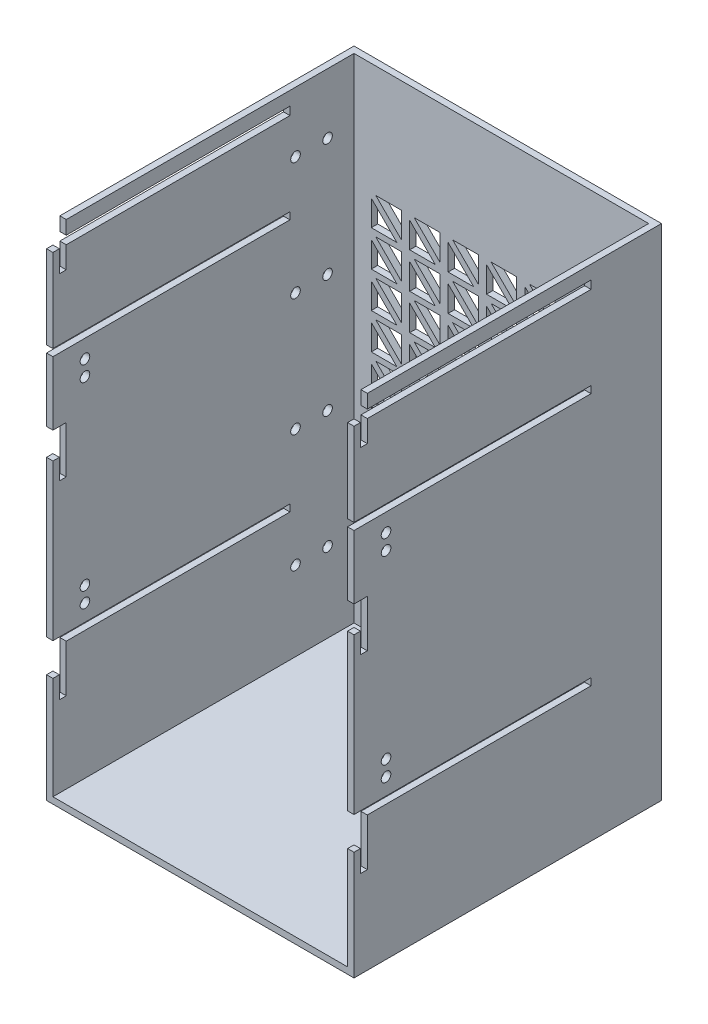
SolidWorks part; units mm, degrees
note: The reader was unsure of these and kept them because the rebuilt part matched: shared geometry of "Sketch7<2>".
ref_plane "Front Plane" through (0, 0, 0) normal (0, 0, 1) x (1, 0, 0)
ref_plane "Top Plane" through (0, 0, 0) normal (0, 1, 0) x (1, 0, 0)
ref_plane "Right Plane" through (0, 0, 0) normal (1, 0, 0) x (0, 0, -1)
sketch "Sketch1" plane through (0, 0, 0) normal (0, 1, 0) x (1, 0, 0)
  line L1 (0, 0) -> (152.4, 0)
  line L2 (0, 0) -> (0, 152.4)
  line L3 (0, 152.4) -> (152.4, 152.4)
  line L4 (152.4, 0) -> (152.4, 152.4)
  dimension "D1" = 152.4
  dimension "D2" = 152.4
extrude "Boss-Extrude1" add sketch "Sketch1" along normal blind 247.65
shell "Shell1" thickness 3.175
ref_plane "Plane1" through (0, 0, -117.475) normal (0, 0, 1) x (1, 0, 0)
sketch "Sketch3" plane through (0, 0, -117.475) normal (0, 0, 1) x (1, 0, 0)
  line L1 (0, 66.675) -> (152.4, 66.675)
  line L2 (0, 66.675) -> (0, 70.1548)
  line L3 (0, 70.1548) -> (152.4, 70.1548)
  line L4 (152.4, 66.675) -> (152.4, 70.1548)
  line L5 (0, 240.8936) -> (152.4, 240.8936)
  line L6 (3.175, 3.175) -> (149.225, 3.175) construction
  line L8 (0, 195.5546) -> (152.4, 195.5546)
  line L9 (0, 195.5546) -> (0, 192.0748)
  line L10 (0, 192.0748) -> (152.4, 192.0748)
  line L11 (152.4, 195.5546) -> (152.4, 192.0748)
  line L12 (152.4, 247.65) -> (152.4, 0) construction
  line L13 (0, 247.65) -> (0, 0) construction
  line L14 (0, 240.8936) -> (0, 236.8296)
  line L15 (0, 236.8296) -> (152.4, 236.8296)
  line L16 (152.4, 240.8936) -> (152.4, 236.8296)
  dimension "D1" = 3.4798
  dimension "D2" = 63.5
  dimension "D3" = 121.92
  dimension "D4" = 41.275
  dimension "D5" = 4.064
extrude "Cut-Extrude1" cut sketch "Sketch3" along normal up to next
sketch "Sketch4" plane through (152.4, 0, 0) normal (1, 0, 0) x (0, 0, -1)
  line L0 (0, 240.8936) -> (117.475, 240.8936) construction
  line L1 (0, 247.65) -> (6.604, 247.65)
  line L2 (0, 247.65) -> (0, 240.8936)
  line L3 (0, 240.8936) -> (6.604, 240.8936)
  line L4 (6.604, 247.65) -> (6.604, 240.8936)
  line L5 (0, 236.8296) -> (117.475, 236.8296) construction
  line L6 (3.175, 236.8296) -> (6.604, 236.8296)
  line L7 (3.175, 236.8296) -> (3.175, 226.06)
  line L8 (3.175, 226.06) -> (6.604, 226.06)
  line L9 (6.604, 236.8296) -> (6.604, 226.06)
  line L10 (0, 236.8296) -> (0, 195.5546) construction
  line L11 (6.604, 66.675) -> (6.604, 43.2054)
  line L12 (0, 66.675) -> (6.604, 66.675)
  line L13 (0, 66.675) -> (0, 53.975)
  line L14 (0, 53.975) -> (3.175, 53.975)
  line L18 (6.604, 43.2054) -> (3.175, 43.2054)
  line L19 (3.175, 53.975) -> (3.175, 43.2054)
  line L20 (0, 247.65) -> (152.4, 247.65) construction
  line L21 (0, 192.0748) -> (0, 70.1548) construction
  line L23 (3.175, 147.32) -> (3.175, 137.16)
  line L24 (3.175, 137.16) -> (6.604, 137.16)
  line L25 (6.604, 160.528) -> (6.604, 137.16)
  line L28 (3.175, 147.32) -> (0, 147.32)
  line L29 (0, 160.528) -> (0, 147.32)
  line L30 (0, 160.528) -> (6.604, 160.528)
  point P29 (3.175, 231.4448)
  dimension "D1" = 3.175
  dimension "D2" = 3.429
  dimension "D3" = 21.59
  dimension "D4" = 88.9
  dimension "D5" = 12.7
  dimension "D6" = 23.368
  dimension "D7" = 13.208
extrude "Cut-Extrude2" cut sketch "Sketch4" against normal through all
sketch "Sketch5" plane through (0, 0, -152.4) normal (0, 0, -1) x (-1, 0, 0)
  line L0 (-152.4, 0) -> (0, 0) construction
  line L1 (-152.4, 247.65) -> (-152.4, 0) construction
  circle A0 centre (-115.8748, 30.1752) radius 4.8895
  dimension "D1" = 9.779
  dimension "D2" = 30.1752
  dimension "D3" = 36.5252
extrude "Cut-Extrude3" cut sketch "Sketch5" against normal up to next
sketch "Sketch6" plane through (0, 0, -149.225) normal (0, 0, 1) x (1, 0, 0)
  line L0 (140.97, 192.0748) -> (140.97, 179.3748)
  line L1 (140.97, 179.3748) -> (128.27, 192.0748)
  line L2 (128.27, 192.0748) -> (140.97, 192.0748)
  line L3 (149.225, 192.0748) -> (149.225, 160.528) construction
  line L4 (126.0249, 192.0748) -> (140.97, 177.1297) construction
  line L5 (138.7249, 177.1297) -> (126.0249, 189.8297)
  line L6 (126.0249, 177.1297) -> (138.7249, 177.1297)
  line L7 (126.0249, 189.8297) -> (126.0249, 177.1297)
  line L8 (149.225, 192.0748) -> (152.4, 192.0748) construction
  line L9 (140.97, 174.2948) -> (140.97, 161.5948)
  line L10 (140.97, 161.5948) -> (128.27, 174.2948)
  line L11 (128.27, 174.2948) -> (140.97, 174.2948)
  line L12 (138.7249, 159.3497) -> (126.0249, 172.0497)
  line L13 (126.0249, 172.0497) -> (126.0249, 159.3497)
  line L14 (126.0249, 159.3497) -> (138.7249, 159.3497)
  line L15 (140.97, 156.5148) -> (140.97, 143.8148)
  line L16 (140.97, 143.8148) -> (128.27, 156.5148)
  line L17 (128.27, 156.5148) -> (140.97, 156.5148)
  line L18 (138.7249, 141.5697) -> (126.0249, 154.2697)
  line L19 (126.0249, 154.2697) -> (126.0249, 141.5697)
  line L20 (126.0249, 141.5697) -> (138.7249, 141.5697)
  line L21 (140.97, 138.7348) -> (140.97, 126.0348)
  line L22 (140.97, 126.0348) -> (128.27, 138.7348)
  line L23 (128.27, 138.7348) -> (140.97, 138.7348)
  line L24 (138.7249, 123.7897) -> (126.0249, 136.4897)
  line L25 (126.0249, 136.4897) -> (126.0249, 123.7897)
  line L26 (126.0249, 123.7897) -> (138.7249, 123.7897)
  line L27 (140.97, 120.9548) -> (140.97, 108.2548)
  line L28 (140.97, 108.2548) -> (128.27, 120.9548)
  line L29 (128.27, 120.9548) -> (140.97, 120.9548)
  line L30 (138.7249, 106.0097) -> (126.0249, 118.7097)
  line L31 (126.0249, 118.7097) -> (126.0249, 106.0097)
  line L32 (126.0249, 106.0097) -> (138.7249, 106.0097)
  line L33 (140.97, 103.1748) -> (140.97, 90.4748)
  line L34 (140.97, 90.4748) -> (128.27, 103.1748)
  line L35 (128.27, 103.1748) -> (140.97, 103.1748)
  line L36 (138.7249, 88.2297) -> (126.0249, 100.9297)
  line L37 (126.0249, 100.9297) -> (126.0249, 88.2297)
  line L38 (126.0249, 88.2297) -> (138.7249, 88.2297)
  line L39 (140.97, 85.3948) -> (140.97, 72.6948)
  line L40 (140.97, 72.6948) -> (128.27, 85.3948)
  line L41 (128.27, 85.3948) -> (140.97, 85.3948)
  line L42 (138.7249, 70.4497) -> (126.0249, 83.1497)
  line L43 (126.0249, 83.1497) -> (126.0249, 70.4497)
  line L44 (126.0249, 70.4497) -> (138.7249, 70.4497)
  line L45 (121.92, 192.0748) -> (121.92, 179.3748)
  line L46 (121.92, 179.3748) -> (109.22, 192.0748)
  line L47 (109.22, 192.0748) -> (121.92, 192.0748)
  line L48 (119.6749, 177.1297) -> (106.9749, 189.8297)
  line L49 (106.9749, 177.1297) -> (119.6749, 177.1297)
  line L50 (106.9749, 189.8297) -> (106.9749, 177.1297)
  line L51 (121.92, 174.2948) -> (121.92, 161.5948)
  line L52 (121.92, 161.5948) -> (109.22, 174.2948)
  line L53 (109.22, 174.2948) -> (121.92, 174.2948)
  line L54 (119.6749, 159.3497) -> (106.9749, 172.0497)
  line L55 (106.9749, 172.0497) -> (106.9749, 159.3497)
  line L56 (106.9749, 159.3497) -> (119.6749, 159.3497)
  line L57 (121.92, 156.5148) -> (121.92, 143.8148)
  line L58 (121.92, 143.8148) -> (109.22, 156.5148)
  line L59 (109.22, 156.5148) -> (121.92, 156.5148)
  line L60 (119.6749, 141.5697) -> (106.9749, 154.2697)
  line L61 (106.9749, 154.2697) -> (106.9749, 141.5697)
  line L62 (106.9749, 141.5697) -> (119.6749, 141.5697)
  line L63 (121.92, 138.7348) -> (121.92, 126.0348)
  line L64 (121.92, 126.0348) -> (109.22, 138.7348)
  line L65 (109.22, 138.7348) -> (121.92, 138.7348)
  line L66 (119.6749, 123.7897) -> (106.9749, 136.4897)
  line L67 (106.9749, 136.4897) -> (106.9749, 123.7897)
  line L68 (106.9749, 123.7897) -> (119.6749, 123.7897)
  line L69 (121.92, 120.9548) -> (121.92, 108.2548)
  line L70 (121.92, 108.2548) -> (109.22, 120.9548)
  line L71 (109.22, 120.9548) -> (121.92, 120.9548)
  line L72 (119.6749, 106.0097) -> (106.9749, 118.7097)
  line L73 (106.9749, 118.7097) -> (106.9749, 106.0097)
  line L74 (106.9749, 106.0097) -> (119.6749, 106.0097)
  line L75 (121.92, 103.1748) -> (121.92, 90.4748)
  line L76 (121.92, 90.4748) -> (109.22, 103.1748)
  line L77 (109.22, 103.1748) -> (121.92, 103.1748)
  line L78 (119.6749, 88.2297) -> (106.9749, 100.9297)
  line L79 (106.9749, 100.9297) -> (106.9749, 88.2297)
  line L80 (106.9749, 88.2297) -> (119.6749, 88.2297)
  line L81 (121.92, 85.3948) -> (121.92, 72.6948)
  line L82 (121.92, 72.6948) -> (109.22, 85.3948)
  line L83 (109.22, 85.3948) -> (121.92, 85.3948)
  line L84 (119.6749, 70.4497) -> (106.9749, 83.1497)
  line L85 (106.9749, 83.1497) -> (106.9749, 70.4497)
  line L86 (106.9749, 70.4497) -> (119.6749, 70.4497)
  line L87 (102.87, 192.0748) -> (102.87, 179.3748)
  line L88 (102.87, 179.3748) -> (90.17, 192.0748)
  line L89 (90.17, 192.0748) -> (102.87, 192.0748)
  line L90 (100.6249, 177.1297) -> (87.9249, 189.8297)
  line L91 (87.9249, 177.1297) -> (100.6249, 177.1297)
  line L92 (87.9249, 189.8297) -> (87.9249, 177.1297)
  line L93 (102.87, 174.2948) -> (102.87, 161.5948)
  line L94 (102.87, 161.5948) -> (90.17, 174.2948)
  line L95 (90.17, 174.2948) -> (102.87, 174.2948)
  line L96 (100.6249, 159.3497) -> (87.9249, 172.0497)
  line L97 (87.9249, 172.0497) -> (87.9249, 159.3497)
  line L98 (87.9249, 159.3497) -> (100.6249, 159.3497)
  line L99 (102.87, 156.5148) -> (102.87, 143.8148)
  line L100 (102.87, 143.8148) -> (90.17, 156.5148)
  line L101 (90.17, 156.5148) -> (102.87, 156.5148)
  line L102 (100.6249, 141.5697) -> (87.9249, 154.2697)
  line L103 (87.9249, 154.2697) -> (87.9249, 141.5697)
  line L104 (87.9249, 141.5697) -> (100.6249, 141.5697)
  line L105 (102.87, 138.7348) -> (102.87, 126.0348)
  line L106 (102.87, 126.0348) -> (90.17, 138.7348)
  line L107 (90.17, 138.7348) -> (102.87, 138.7348)
  line L108 (100.6249, 123.7897) -> (87.9249, 136.4897)
  line L109 (87.9249, 136.4897) -> (87.9249, 123.7897)
  line L110 (87.9249, 123.7897) -> (100.6249, 123.7897)
  line L111 (102.87, 120.9548) -> (102.87, 108.2548)
  line L112 (102.87, 108.2548) -> (90.17, 120.9548)
  line L113 (90.17, 120.9548) -> (102.87, 120.9548)
  line L114 (100.6249, 106.0097) -> (87.9249, 118.7097)
  line L115 (87.9249, 118.7097) -> (87.9249, 106.0097)
  line L116 (87.9249, 106.0097) -> (100.6249, 106.0097)
  line L117 (102.87, 103.1748) -> (102.87, 90.4748)
  line L118 (102.87, 90.4748) -> (90.17, 103.1748)
  line L119 (90.17, 103.1748) -> (102.87, 103.1748)
  line L120 (100.6249, 88.2297) -> (87.9249, 100.9297)
  line L121 (87.9249, 100.9297) -> (87.9249, 88.2297)
  line L122 (87.9249, 88.2297) -> (100.6249, 88.2297)
  line L123 (102.87, 85.3948) -> (102.87, 72.6948)
  line L124 (102.87, 72.6948) -> (90.17, 85.3948)
  line L125 (90.17, 85.3948) -> (102.87, 85.3948)
  line L126 (100.6249, 70.4497) -> (87.9249, 83.1497)
  line L127 (87.9249, 83.1497) -> (87.9249, 70.4497)
  line L128 (87.9249, 70.4497) -> (100.6249, 70.4497)
  line L129 (83.82, 192.0748) -> (83.82, 179.3748)
  line L130 (83.82, 179.3748) -> (71.12, 192.0748)
  line L131 (71.12, 192.0748) -> (83.82, 192.0748)
  line L132 (81.5749, 177.1297) -> (68.8749, 189.8297)
  line L133 (68.8749, 177.1297) -> (81.5749, 177.1297)
  line L134 (68.8749, 189.8297) -> (68.8749, 177.1297)
  line L135 (83.82, 174.2948) -> (83.82, 161.5948)
  line L136 (83.82, 161.5948) -> (71.12, 174.2948)
  line L137 (71.12, 174.2948) -> (83.82, 174.2948)
  line L138 (81.5749, 159.3497) -> (68.8749, 172.0497)
  line L139 (68.8749, 172.0497) -> (68.8749, 159.3497)
  line L140 (68.8749, 159.3497) -> (81.5749, 159.3497)
  line L141 (83.82, 156.5148) -> (83.82, 143.8148)
  line L142 (83.82, 143.8148) -> (71.12, 156.5148)
  line L143 (71.12, 156.5148) -> (83.82, 156.5148)
  line L144 (81.5749, 141.5697) -> (68.8749, 154.2697)
  line L145 (68.8749, 154.2697) -> (68.8749, 141.5697)
  line L146 (68.8749, 141.5697) -> (81.5749, 141.5697)
  line L147 (83.82, 138.7348) -> (83.82, 126.0348)
  line L148 (83.82, 126.0348) -> (71.12, 138.7348)
  line L149 (71.12, 138.7348) -> (83.82, 138.7348)
  line L150 (81.5749, 123.7897) -> (68.8749, 136.4897)
  line L151 (68.8749, 136.4897) -> (68.8749, 123.7897)
  line L152 (68.8749, 123.7897) -> (81.5749, 123.7897)
  line L153 (83.82, 120.9548) -> (83.82, 108.2548)
  line L154 (83.82, 108.2548) -> (71.12, 120.9548)
  line L155 (71.12, 120.9548) -> (83.82, 120.9548)
  line L156 (81.5749, 106.0097) -> (68.8749, 118.7097)
  line L157 (68.8749, 118.7097) -> (68.8749, 106.0097)
  line L158 (68.8749, 106.0097) -> (81.5749, 106.0097)
  line L159 (83.82, 103.1748) -> (83.82, 90.4748)
  line L160 (83.82, 90.4748) -> (71.12, 103.1748)
  line L161 (71.12, 103.1748) -> (83.82, 103.1748)
  line L162 (81.5749, 88.2297) -> (68.8749, 100.9297)
  line L163 (68.8749, 100.9297) -> (68.8749, 88.2297)
  line L164 (68.8749, 88.2297) -> (81.5749, 88.2297)
  line L165 (83.82, 85.3948) -> (83.82, 72.6948)
  line L166 (83.82, 72.6948) -> (71.12, 85.3948)
  line L167 (71.12, 85.3948) -> (83.82, 85.3948)
  line L168 (81.5749, 70.4497) -> (68.8749, 83.1497)
  line L169 (68.8749, 83.1497) -> (68.8749, 70.4497)
  line L170 (68.8749, 70.4497) -> (81.5749, 70.4497)
  line L171 (64.77, 192.0748) -> (64.77, 179.3748)
  line L172 (64.77, 179.3748) -> (52.07, 192.0748)
  line L173 (52.07, 192.0748) -> (64.77, 192.0748)
  line L174 (62.5249, 177.1297) -> (49.8249, 189.8297)
  line L175 (49.8249, 177.1297) -> (62.5249, 177.1297)
  line L176 (49.8249, 189.8297) -> (49.8249, 177.1297)
  line L177 (64.77, 174.2948) -> (64.77, 161.5948)
  line L178 (64.77, 161.5948) -> (52.07, 174.2948)
  line L179 (52.07, 174.2948) -> (64.77, 174.2948)
  line L180 (62.5249, 159.3497) -> (49.8249, 172.0497)
  line L181 (49.8249, 172.0497) -> (49.8249, 159.3497)
  line L182 (49.8249, 159.3497) -> (62.5249, 159.3497)
  line L183 (64.77, 156.5148) -> (64.77, 143.8148)
  line L184 (64.77, 143.8148) -> (52.07, 156.5148)
  line L185 (52.07, 156.5148) -> (64.77, 156.5148)
  line L186 (62.5249, 141.5697) -> (49.8249, 154.2697)
  line L187 (49.8249, 154.2697) -> (49.8249, 141.5697)
  line L188 (49.8249, 141.5697) -> (62.5249, 141.5697)
  line L189 (64.77, 138.7348) -> (64.77, 126.0348)
  line L190 (64.77, 126.0348) -> (52.07, 138.7348)
  line L191 (52.07, 138.7348) -> (64.77, 138.7348)
  line L192 (62.5249, 123.7897) -> (49.8249, 136.4897)
  line L193 (49.8249, 136.4897) -> (49.8249, 123.7897)
  line L194 (49.8249, 123.7897) -> (62.5249, 123.7897)
  line L195 (64.77, 120.9548) -> (64.77, 108.2548)
  line L196 (64.77, 108.2548) -> (52.07, 120.9548)
  line L197 (52.07, 120.9548) -> (64.77, 120.9548)
  line L198 (62.5249, 106.0097) -> (49.8249, 118.7097)
  line L199 (49.8249, 118.7097) -> (49.8249, 106.0097)
  line L200 (49.8249, 106.0097) -> (62.5249, 106.0097)
  line L201 (64.77, 103.1748) -> (64.77, 90.4748)
  line L202 (64.77, 90.4748) -> (52.07, 103.1748)
  line L203 (52.07, 103.1748) -> (64.77, 103.1748)
  line L204 (62.5249, 88.2297) -> (49.8249, 100.9297)
  line L205 (49.8249, 100.9297) -> (49.8249, 88.2297)
  line L206 (49.8249, 88.2297) -> (62.5249, 88.2297)
  line L207 (64.77, 85.3948) -> (64.77, 72.6948)
  line L208 (64.77, 72.6948) -> (52.07, 85.3948)
  line L209 (52.07, 85.3948) -> (64.77, 85.3948)
  line L210 (62.5249, 70.4497) -> (49.8249, 83.1497)
  line L211 (49.8249, 83.1497) -> (49.8249, 70.4497)
  line L212 (49.8249, 70.4497) -> (62.5249, 70.4497)
  line L213 (45.72, 192.0748) -> (45.72, 179.3748)
  line L214 (45.72, 179.3748) -> (33.02, 192.0748)
  line L215 (33.02, 192.0748) -> (45.72, 192.0748)
  line L216 (43.4749, 177.1297) -> (30.7749, 189.8297)
  line L217 (30.7749, 177.1297) -> (43.4749, 177.1297)
  line L218 (30.7749, 189.8297) -> (30.7749, 177.1297)
  line L219 (45.72, 174.2948) -> (45.72, 161.5948)
  line L220 (45.72, 161.5948) -> (33.02, 174.2948)
  line L221 (33.02, 174.2948) -> (45.72, 174.2948)
  line L222 (43.4749, 159.3497) -> (30.7749, 172.0497)
  line L223 (30.7749, 172.0497) -> (30.7749, 159.3497)
  line L224 (30.7749, 159.3497) -> (43.4749, 159.3497)
  line L225 (45.72, 156.5148) -> (45.72, 143.8148)
  line L226 (45.72, 143.8148) -> (33.02, 156.5148)
  line L227 (33.02, 156.5148) -> (45.72, 156.5148)
  line L228 (43.4749, 141.5697) -> (30.7749, 154.2697)
  line L229 (30.7749, 154.2697) -> (30.7749, 141.5697)
  line L230 (30.7749, 141.5697) -> (43.4749, 141.5697)
  line L231 (45.72, 138.7348) -> (45.72, 126.0348)
  line L232 (45.72, 126.0348) -> (33.02, 138.7348)
  line L233 (33.02, 138.7348) -> (45.72, 138.7348)
  line L234 (43.4749, 123.7897) -> (30.7749, 136.4897)
  line L235 (30.7749, 136.4897) -> (30.7749, 123.7897)
  line L236 (30.7749, 123.7897) -> (43.4749, 123.7897)
  line L237 (45.72, 120.9548) -> (45.72, 108.2548)
  line L238 (45.72, 108.2548) -> (33.02, 120.9548)
  line L239 (33.02, 120.9548) -> (45.72, 120.9548)
  line L240 (43.4749, 106.0097) -> (30.7749, 118.7097)
  line L241 (30.7749, 118.7097) -> (30.7749, 106.0097)
  line L242 (30.7749, 106.0097) -> (43.4749, 106.0097)
  line L243 (45.72, 103.1748) -> (45.72, 90.4748)
  line L244 (45.72, 90.4748) -> (33.02, 103.1748)
  line L245 (33.02, 103.1748) -> (45.72, 103.1748)
  line L246 (43.4749, 88.2297) -> (30.7749, 100.9297)
  line L247 (30.7749, 100.9297) -> (30.7749, 88.2297)
  line L248 (30.7749, 88.2297) -> (43.4749, 88.2297)
  line L249 (45.72, 85.3948) -> (45.72, 72.6948)
  line L250 (45.72, 72.6948) -> (33.02, 85.3948)
  line L251 (33.02, 85.3948) -> (45.72, 85.3948)
  line L252 (43.4749, 70.4497) -> (30.7749, 83.1497)
  line L253 (30.7749, 83.1497) -> (30.7749, 70.4497)
  line L254 (30.7749, 70.4497) -> (43.4749, 70.4497)
  line L255 (26.67, 192.0748) -> (26.67, 179.3748)
  line L256 (26.67, 179.3748) -> (13.97, 192.0748)
  line L257 (13.97, 192.0748) -> (26.67, 192.0748)
  line L258 (24.4249, 177.1297) -> (11.7249, 189.8297)
  line L259 (11.7249, 177.1297) -> (24.4249, 177.1297)
  line L260 (11.7249, 189.8297) -> (11.7249, 177.1297)
  line L261 (26.67, 174.2948) -> (26.67, 161.5948)
  line L262 (26.67, 161.5948) -> (13.97, 174.2948)
  line L263 (13.97, 174.2948) -> (26.67, 174.2948)
  line L264 (24.4249, 159.3497) -> (11.7249, 172.0497)
  line L265 (11.7249, 172.0497) -> (11.7249, 159.3497)
  line L266 (11.7249, 159.3497) -> (24.4249, 159.3497)
  line L267 (26.67, 156.5148) -> (26.67, 143.8148)
  line L268 (26.67, 143.8148) -> (13.97, 156.5148)
  line L269 (13.97, 156.5148) -> (26.67, 156.5148)
  line L270 (24.4249, 141.5697) -> (11.7249, 154.2697)
  line L271 (11.7249, 154.2697) -> (11.7249, 141.5697)
  line L272 (11.7249, 141.5697) -> (24.4249, 141.5697)
  line L273 (26.67, 138.7348) -> (26.67, 126.0348)
  line L274 (26.67, 126.0348) -> (13.97, 138.7348)
  line L275 (13.97, 138.7348) -> (26.67, 138.7348)
  line L276 (24.4249, 123.7897) -> (11.7249, 136.4897)
  line L277 (11.7249, 136.4897) -> (11.7249, 123.7897)
  line L278 (11.7249, 123.7897) -> (24.4249, 123.7897)
  line L279 (26.67, 120.9548) -> (26.67, 108.2548)
  line L280 (26.67, 108.2548) -> (13.97, 120.9548)
  line L281 (13.97, 120.9548) -> (26.67, 120.9548)
  line L282 (24.4249, 106.0097) -> (11.7249, 118.7097)
  line L283 (11.7249, 118.7097) -> (11.7249, 106.0097)
  line L284 (11.7249, 106.0097) -> (24.4249, 106.0097)
  line L285 (26.67, 103.1748) -> (26.67, 90.4748)
  line L286 (26.67, 90.4748) -> (13.97, 103.1748)
  line L287 (13.97, 103.1748) -> (26.67, 103.1748)
  line L288 (24.4249, 88.2297) -> (11.7249, 100.9297)
  line L289 (11.7249, 100.9297) -> (11.7249, 88.2297)
  line L290 (11.7249, 88.2297) -> (24.4249, 88.2297)
  line L291 (26.67, 85.3948) -> (26.67, 72.6948)
  line L292 (26.67, 72.6948) -> (13.97, 85.3948)
  line L293 (13.97, 85.3948) -> (26.67, 85.3948)
  line L294 (24.4249, 70.4497) -> (11.7249, 83.1497)
  line L295 (11.7249, 83.1497) -> (11.7249, 70.4497)
  line L296 (11.7249, 70.4497) -> (24.4249, 70.4497)
  line L297 (149.225, 60.325) -> (3.175, 60.325) construction
  line L298 (149.225, 247.65) -> (149.225, 3.175) construction
  line L299 (3.175, 43.2054) -> (3.175, 66.675) construction
  line L300 (149.225, 3.175) -> (3.175, 3.175) construction
  line L301 (140.97, 60.325) -> (140.97, 47.625)
  line L302 (140.97, 47.625) -> (128.27, 60.325)
  line L303 (128.27, 60.325) -> (140.97, 60.325)
  line L304 (126.0249, 60.325) -> (147.432, 38.918) construction
  line L305 (126.0249, 58.0799) -> (126.0249, 45.3799)
  line L306 (138.7249, 45.3799) -> (126.0249, 58.0799)
  line L307 (126.0249, 45.3799) -> (138.7249, 45.3799)
  line L308 (121.92, 60.325) -> (121.92, 47.625)
  line L309 (121.92, 47.625) -> (109.22, 60.325)
  line L310 (109.22, 60.325) -> (121.92, 60.325)
  line L311 (106.9749, 58.0799) -> (106.9749, 45.3799)
  line L312 (119.6749, 45.3799) -> (106.9749, 58.0799)
  line L313 (106.9749, 45.3799) -> (119.6749, 45.3799)
  line L314 (102.87, 60.325) -> (102.87, 47.625)
  line L315 (102.87, 47.625) -> (90.17, 60.325)
  line L316 (90.17, 60.325) -> (102.87, 60.325)
  line L317 (87.9249, 58.0799) -> (87.9249, 45.3799)
  line L318 (100.6249, 45.3799) -> (87.9249, 58.0799)
  line L319 (87.9249, 45.3799) -> (100.6249, 45.3799)
  line L320 (83.82, 60.325) -> (83.82, 47.625)
  line L321 (83.82, 47.625) -> (71.12, 60.325)
  line L322 (71.12, 60.325) -> (83.82, 60.325)
  line L323 (68.8749, 58.0799) -> (68.8749, 45.3799)
  line L324 (81.5749, 45.3799) -> (68.8749, 58.0799)
  line L325 (68.8749, 45.3799) -> (81.5749, 45.3799)
  line L326 (64.77, 60.325) -> (64.77, 47.625)
  line L327 (64.77, 47.625) -> (52.07, 60.325)
  line L328 (52.07, 60.325) -> (64.77, 60.325)
  line L329 (49.8249, 58.0799) -> (49.8249, 45.3799)
  line L330 (62.5249, 45.3799) -> (49.8249, 58.0799)
  line L331 (49.8249, 45.3799) -> (62.5249, 45.3799)
  line L332 (45.72, 60.325) -> (45.72, 47.625)
  line L333 (45.72, 47.625) -> (33.02, 60.325)
  line L334 (33.02, 60.325) -> (45.72, 60.325)
  line L335 (30.7749, 58.0799) -> (30.7749, 45.3799)
  line L336 (43.4749, 45.3799) -> (30.7749, 58.0799)
  line L337 (30.7749, 45.3799) -> (43.4749, 45.3799)
  line L338 (26.67, 60.325) -> (26.67, 47.625)
  line L339 (26.67, 47.625) -> (13.97, 60.325)
  line L340 (13.97, 60.325) -> (26.67, 60.325)
  line L341 (11.7249, 58.0799) -> (11.7249, 45.3799)
  line L342 (24.4249, 45.3799) -> (11.7249, 58.0799)
  line L343 (11.7249, 45.3799) -> (24.4249, 45.3799)
  line L344 (102.87, 41.275) -> (102.87, 28.575)
  line L345 (102.87, 28.575) -> (90.17, 41.275)
  line L346 (90.17, 41.275) -> (102.87, 41.275)
  line L347 (87.9249, 39.0299) -> (87.9249, 26.3299)
  line L348 (100.6249, 26.3299) -> (87.9249, 39.0299)
  line L349 (87.9249, 26.3299) -> (100.6249, 26.3299)
  line L350 (83.82, 41.275) -> (83.82, 28.575)
  line L351 (83.82, 28.575) -> (71.12, 41.275)
  line L352 (71.12, 41.275) -> (83.82, 41.275)
  line L353 (68.8749, 39.0299) -> (68.8749, 26.3299)
  line L354 (81.5749, 26.3299) -> (68.8749, 39.0299)
  line L355 (68.8749, 26.3299) -> (81.5749, 26.3299)
  line L356 (64.77, 41.275) -> (64.77, 28.575)
  line L357 (64.77, 28.575) -> (52.07, 41.275)
  line L358 (52.07, 41.275) -> (64.77, 41.275)
  line L359 (49.8249, 39.0299) -> (49.8249, 26.3299)
  line L360 (62.5249, 26.3299) -> (49.8249, 39.0299)
  line L361 (49.8249, 26.3299) -> (62.5249, 26.3299)
  line L362 (45.72, 41.275) -> (45.72, 28.575)
  line L363 (45.72, 28.575) -> (33.02, 41.275)
  line L364 (33.02, 41.275) -> (45.72, 41.275)
  line L365 (30.7749, 39.0299) -> (30.7749, 26.3299)
  line L366 (43.4749, 26.3299) -> (30.7749, 39.0299)
  line L367 (30.7749, 26.3299) -> (43.4749, 26.3299)
  line L368 (26.67, 41.275) -> (26.67, 28.575)
  line L369 (26.67, 28.575) -> (13.97, 41.275)
  line L370 (13.97, 41.275) -> (26.67, 41.275)
  line L371 (11.7249, 39.0299) -> (11.7249, 26.3299)
  line L372 (24.4249, 26.3299) -> (11.7249, 39.0299)
  line L373 (11.7249, 26.3299) -> (24.4249, 26.3299)
  line L374 (126.0249, 26.3299) -> (138.7249, 26.3299)
  line L375 (126.0249, 39.0299) -> (126.0249, 26.3299)
  line L376 (138.7249, 26.3299) -> (126.0249, 39.0299)
  line L377 (140.97, 28.575) -> (128.27, 41.275)
  line L378 (128.27, 41.275) -> (140.97, 41.275)
  line L379 (140.97, 41.275) -> (140.97, 28.575)
  line L380 (102.87, 22.225) -> (102.87, 9.525)
  line L381 (102.87, 9.525) -> (90.17, 22.225)
  line L382 (90.17, 22.225) -> (102.87, 22.225)
  line L383 (87.9249, 19.9799) -> (87.9249, 7.2799)
  line L384 (100.6249, 7.2799) -> (87.9249, 19.9799)
  line L385 (87.9249, 7.2799) -> (100.6249, 7.2799)
  line L386 (83.82, 22.225) -> (83.82, 9.525)
  line L387 (83.82, 9.525) -> (71.12, 22.225)
  line L388 (71.12, 22.225) -> (83.82, 22.225)
  line L389 (68.8749, 19.9799) -> (68.8749, 7.2799)
  line L390 (81.5749, 7.2799) -> (68.8749, 19.9799)
  line L391 (68.8749, 7.2799) -> (81.5749, 7.2799)
  line L392 (64.77, 22.225) -> (64.77, 9.525)
  line L393 (64.77, 9.525) -> (52.07, 22.225)
  line L394 (52.07, 22.225) -> (64.77, 22.225)
  line L395 (49.8249, 19.9799) -> (49.8249, 7.2799)
  line L396 (62.5249, 7.2799) -> (49.8249, 19.9799)
  line L397 (49.8249, 7.2799) -> (62.5249, 7.2799)
  line L398 (45.72, 22.225) -> (45.72, 9.525)
  line L399 (45.72, 9.525) -> (33.02, 22.225)
  line L400 (33.02, 22.225) -> (45.72, 22.225)
  line L401 (30.7749, 19.9799) -> (30.7749, 7.2799)
  line L402 (43.4749, 7.2799) -> (30.7749, 19.9799)
  line L403 (30.7749, 7.2799) -> (43.4749, 7.2799)
  line L404 (26.67, 22.225) -> (26.67, 9.525)
  line L405 (26.67, 9.525) -> (13.97, 22.225)
  line L406 (13.97, 22.225) -> (26.67, 22.225)
  line L407 (11.7249, 19.9799) -> (11.7249, 7.2799)
  line L408 (24.4249, 7.2799) -> (11.7249, 19.9799)
  line L409 (11.7249, 7.2799) -> (24.4249, 7.2799)
  line L410 (126.0249, 7.2799) -> (138.7249, 7.2799)
  line L411 (126.0249, 19.9799) -> (126.0249, 7.2799)
  line L412 (138.7249, 7.2799) -> (126.0249, 19.9799)
  line L413 (140.97, 9.525) -> (128.27, 22.225)
  line L414 (128.27, 22.225) -> (140.97, 22.225)
  line L415 (140.97, 22.225) -> (140.97, 9.525)
  dimension "D1" = 8.255
  dimension "D2" = 12.7
  dimension "D3" = 1.5875
  dimension "D4" = 7
  dimension "D6" = 57.15
  dimension "D7" = 1.5875
  dimension "D5" = 7
  dimension "D8" = 7
  dimension "D9" = 3
extrude "Cut-Extrude4" cut sketch "Sketch6" against normal up to next (3.175 mm away)
sketch "Sketch7" plane through (0, 0, 0) normal (-1, 0, 0) x (0, 0, 1)
  line L1 (0, 195.5546) -> (-117.475, 195.5546) construction
  line L2 (0, 70.1548) -> (-117.475, 70.1548) construction
  line L3 (0, 192.0748) -> (0, 160.528) construction
  circle A0 centre (-136.111, 217.7796) radius 2.3813
  circle A1 centre (-120.236, 217.7796) radius 2.3813
  circle A2 centre (-136.111, 159.3596) radius 2.3813
  circle A3 centre (-120.236, 159.3596) radius 2.3813
  circle A4 centre (-136.111, 100.9396) radius 2.3813
  circle A5 centre (-120.236, 100.9396) radius 2.3813
  circle A6 centre (-136.111, 42.5196) radius 2.3813
  circle A7 centre (-120.236, 42.5196) radius 2.3813
  circle A8 centre (-15.875, 183.1848) radius 2.3813
  circle A9 centre (-15.875, 175.5648) radius 2.3813
  circle A10 centre (-15.875, 78.4098) radius 2.3812
  circle A11 centre (-15.875, 86.0298) radius 2.3812
  dimension "D1" = 4.7625
  dimension "D2" = 113.03
  dimension "D3" = 15.875
  dimension "D4" = 22.225
  dimension "D6" = 7.62
  dimension "D8" = 15.875
  dimension "D5" = 4
  dimension "D7" = 2
extrude "Cut-Extrude5" cut sketch "Sketch7" against normal up to next
extrude "Cut-Extrude6" cut sketch "Sketch7<2>" against normal through all contours A8 | A9 | A11 | A10
sketch "Sketch7<2>" plane through (0, 0, 0) normal (-1, 0, 0) x (0, 0, 1) same geometry as "Sketch7"
sketch "Sketch8" plane through (0, 0, -149.225) normal (0, 0, 1) x (1, 0, 0)
  line L0 (0, 63.754) -> (152.4, 63.754) construction
  line L1 (0, 43.2054) -> (0, 66.675) construction
  line L2 (152.4, 43.2054) -> (152.4, 66.675) construction
  line L3 (149.225, 247.65) -> (3.175, 247.65) construction
  line L4 (3.175, 43.2054) -> (3.175, 66.675) construction
  line L9 (76.2, 3.175) -> (76.2, 63.754) construction
  line L10 (149.225, 3.175) -> (3.175, 3.175) construction
  circle A0 centre (6.35, 68.5165) radius 2.3812
  circle A1 centre (6.35, 58.9915) radius 2.3812
  circle A2 centre (146.05, 58.9915) radius 2.3813
  circle A3 centre (146.05, 68.5165) radius 2.3813
  dimension "D3" = 4.7625
  dimension "D1" = 183.896
  dimension "D2" = 9.525
  dimension "D4" = 4.7625
  dimension "D5" = 3.175
extrude "Cut-Extrude8" cut sketch "Sketch8" against normal through all
sketch "Sketch10" plane through (0, 0, 0) normal (0, 0, 1) x (1, 0, 0)
  line L1 (0, 247.65) -> (171.7818, 247.65) construction
  line L2 (0, 247.65) -> (0, 63.754) construction
  line L3 (0, 63.754) -> (171.7818, 63.754) construction
  line L4 (171.7818, 247.65) -> (171.7818, 63.754) construction
  line L5 (165.5519, 63.754) -> (-36.0276, 63.754)
  line L6 (165.5519, 63.754) -> (165.5519, -13.6177)
  line L7 (165.5519, -13.6177) -> (-36.0276, -13.6177)
  line L8 (-36.0276, 63.754) -> (-36.0276, -13.6177)
  dimension "D1" = 183.896
